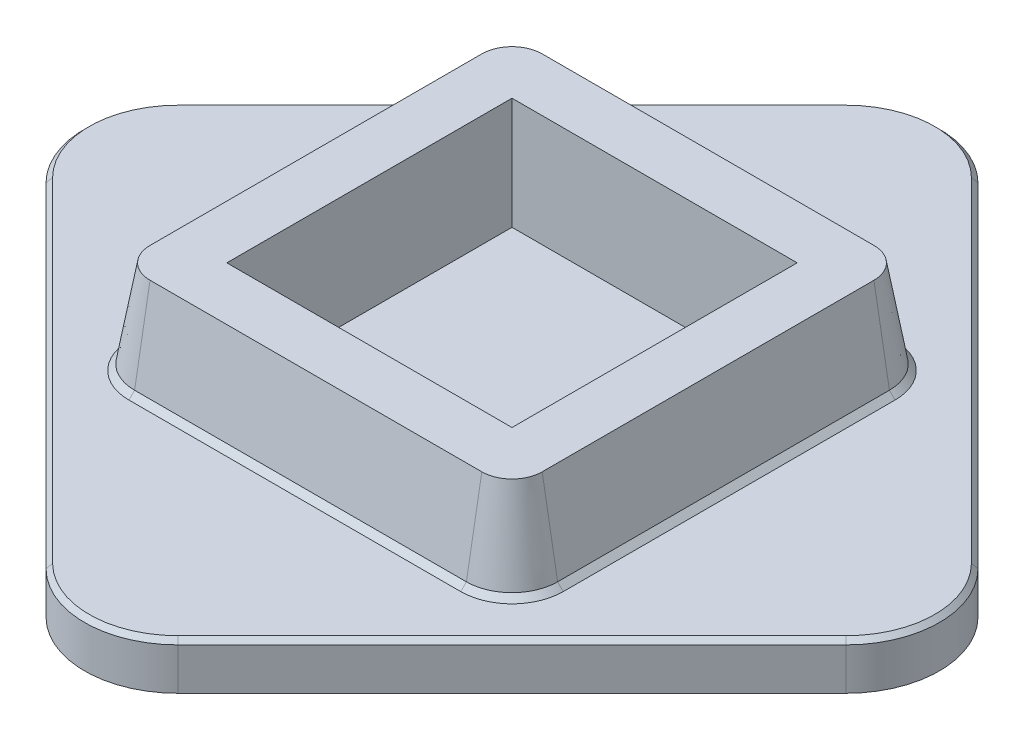
SolidWorks part; units mm, degrees
note: The reader was unsure of these and kept them because the rebuilt part matched: shared geometry of "Sketch1<4>", "Sketch1<5>".
ref_plane "Front Plane" through (0, 0, 0) normal (0, 0, 1) x (1, 0, 0)
ref_plane "Top Plane" through (0, 0, 0) normal (0, 1, 0) x (1, 0, 0)
ref_plane "Right Plane" through (0, 0, 0) normal (1, 0, 0) x (0, 0, -1)
sketch "Sketch1" plane through (0, 0, 0) normal (0, 1, 0) x (1, 0, 0)
  line L0 (7.0711, -42.9289) -> (42.9289, -7.0711)
  line L5 (-7.0711, -42.9289) -> (-42.9289, -7.0711)
  line L6 (42.9289, 7.0711) -> (7.0711, 42.9289)
  line L11 (15, -15) -> (-15, 15) construction
  line L12 (15, 15) -> (-15, -15) construction
  line L13 (17.8, -22.8) -> (-17.8, -22.8)
  line L14 (22.8, -17.8) -> (22.8, 17.8)
  line L15 (17.8, 22.8) -> (-17.8, 22.8)
  line L16 (-22.8, -17.8) -> (-22.8, 17.8)
  line L17 (22.8, -22.8) -> (-22.8, 22.8) construction
  line L18 (22.8, 22.8) -> (-22.8, -22.8) construction
  line L19 (-42.9289, 7.0711) -> (-7.0711, 42.9289)
  line L20 (0, -50) -> (0, 50) construction
  line L21 (50, 0) -> (-50, 0) construction
  line L26 (15.3, 15.3) -> (-15.3, 15.3)
  line L27 (-15.3, 15.3) -> (-15.3, -15.3)
  line L28 (-15.3, -15.3) -> (15.3, -15.3)
  line L29 (15.3, -15.3) -> (15.3, 15.3)
  line L30 (15.3, 15.3) -> (-15.3, 15.3)
  line L31 (-15.3, 15.3) -> (-15.3, -15.3)
  line L32 (-15.3, -15.3) -> (15.3, -15.3)
  line L33 (15.3, -15.3) -> (15.3, 15.3)
  arc A0 (-17.8, -22.8) -> (-22.8, -17.8) centre (-17.8, -17.8) cw
  arc A1 (17.8, -22.8) -> (22.8, -17.8) centre (17.8, -17.8) ccw
  arc A2 (22.8, 17.8) -> (17.8, 22.8) centre (17.8, 17.8) ccw
  arc A3 (-17.8, 22.8) -> (-22.8, 17.8) centre (-17.8, 17.8) ccw
  arc A8 (-42.9289, -7.0711) -> (-42.9289, 7.0711) centre (-35.8579, 0) cw
  arc A9 (-7.0711, -42.9289) -> (7.0711, -42.9289) centre (0, -35.8579) ccw
  arc A10 (42.9289, -7.0711) -> (42.9289, 7.0711) centre (35.8579, 0) ccw
  arc A11 (7.0711, 42.9289) -> (-7.0711, 42.9289) centre (0, 35.8579) ccw
  point P0 (0, 0)
  point P1 (0, 0)
  point P2 (0, 0)
  point P3 (0, 0)
  point P4 (0, 0)
  point P6 (0, 0)
  point P12 (0, 0)
  dimension "D3" = 5
  dimension "D4" = 100
  dimension "D6" = 10
  dimension "D1" = 7.5
  dimension "D2" = 0.3
  dimension "D5" = 5.1823
extrude "Boss-Extrude1" add sketch "Sketch1" along normal blind 5
extrude "Boss-Extrude2" add sketch "Sketch1<4>" along normal blind 10 draft 10 from surface at 5 starting at face at (0, 5, 0)
sketch "Sketch1<4>" plane through (0, 0, 0) normal (0, 1, 0) x (1, 0, 0) same geometry as "Sketch1"
extrude "Cut-Extrude1" cut sketch "Sketch1<5>" along normal up to surface (12 mm away) from offset 3 up to face at (0, 15, 0)
sketch "Sketch1<5>" plane through (0, 0, 0) normal (0, 1, 0) x (1, 0, 0) same geometry as "Sketch1"
chamfer "Chamfer1" distance 0.5 angle 45 16 edges at (-25, 5, -25) (0, 5, -22.8) (-21.3355, 5, -21.3355) (-22.8, 5, 0) (-21.3355, 5, 21.3355) (0, 5, 22.8) (21.3355, 5, 21.3355) (22.8, 5, 0) (21.3355, 5, -21.3355) (45.8579, 5, 0) (25, 5, 25) (0, 5, 45.8579) (-25, 5, 25) (-45.8579, 5, 0) (0, 5, -45.8579) (25, 5, -25)
